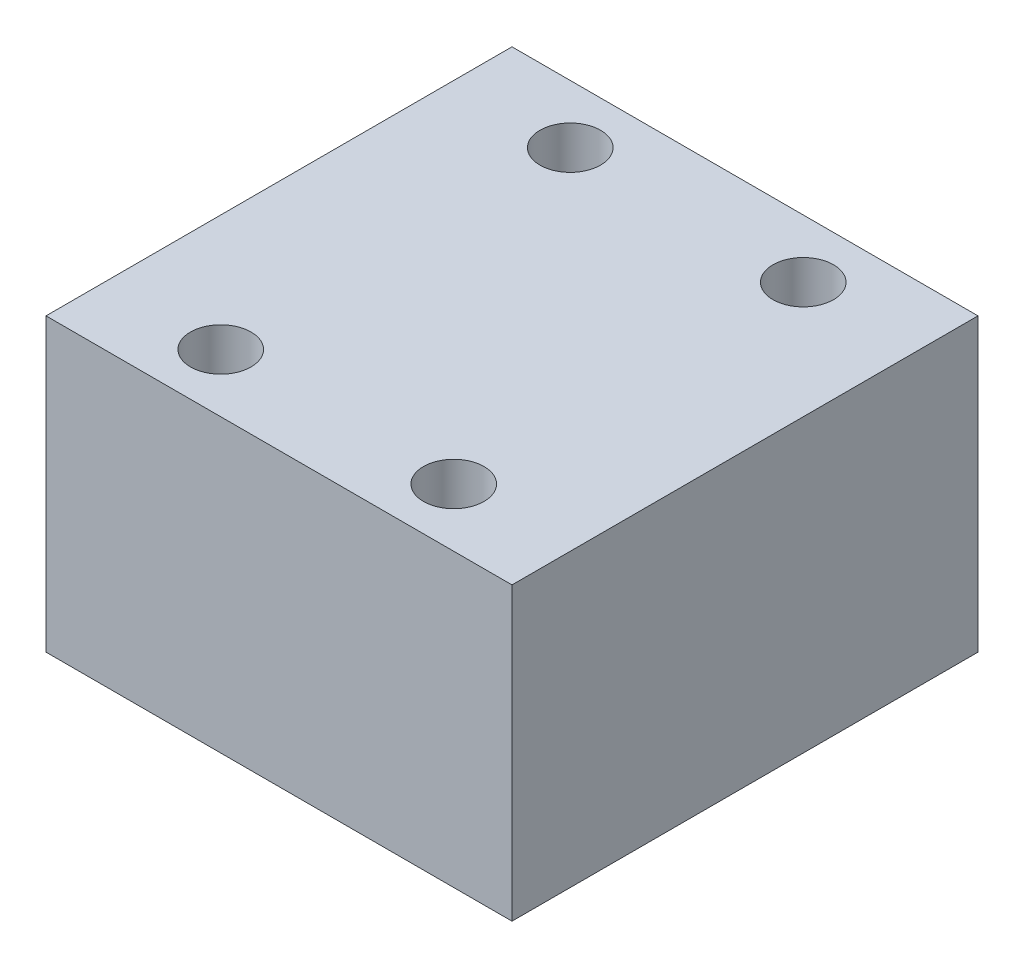
SolidWorks part; units mm, degrees
ref_plane "前视基准面" through (0, 0, 0) normal (0, 0, 1) x (1, 0, 0)
ref_plane "上视基准面" through (0, 0, 0) normal (0, 1, 0) x (1, 0, 0)
ref_plane "右视基准面" through (0, 0, 0) normal (1, 0, 0) x (0, 0, -1)
sketch "草图1" plane through (0, 0, 0) normal (0, 1, 0) x (1, 0, 0)
  line L1 (-20, 20) -> (20, 20)
  line L2 (-20, 20) -> (-20, -20)
  line L3 (-20, -20) -> (20, -20)
  line L4 (20, 20) -> (20, -20)
  line L5 (-20, 20) -> (20, -20) construction
  line L6 (-20, -20) -> (20, 20) construction
  point P0 (0, 0)
extrude "凸台-拉伸1" add sketch "草图1" along normal blind 12.5 and the other way blind 12.5
sketch "草图2" plane through (0, 12.5, 0) normal (0, 1, 0) x (1, 0, 0)
  circle A0 centre (-10, 15) radius 2.6
  circle A2 centre (10, 15) radius 2.6
  circle A3 centre (-10, -15) radius 2.6
  circle A4 centre (10, -15) radius 2.6
  dimension "D1" = 2
  dimension "D2" = 2
  dimension "D3" = 2
extrude "切除-拉伸3" cut sketch "草图2" against normal through all
